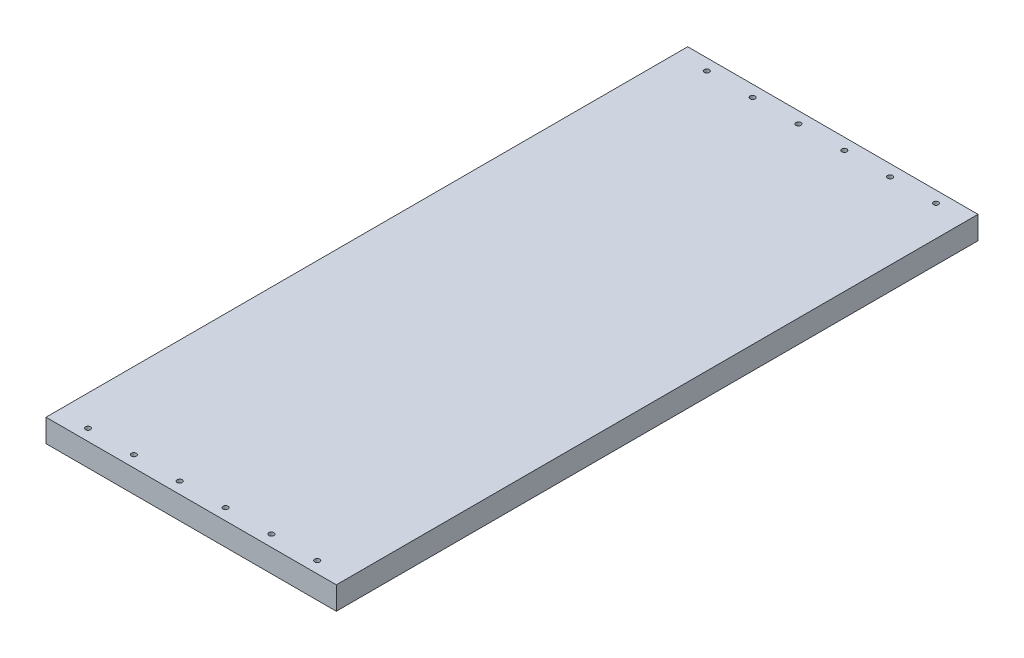
SolidWorks part; units mm, degrees
ref_plane "Front Plane" through (0, 0, 0) normal (0, 0, 1) x (1, 0, 0)
ref_plane "Top Plane" through (0, 0, 0) normal (0, 1, 0) x (1, 0, 0)
ref_plane "Right Plane" through (0, 0, 0) normal (1, 0, 0) x (0, 0, -1)
sketch "Sketch2" plane through (0, 0, 0) normal (0, 0, 1) x (1, 0, 0)
  line L1 (241.3, -19.05) -> (-241.3, -19.05)
  line L2 (241.3, -19.05) -> (241.3, 19.05)
  line L3 (241.3, 19.05) -> (-241.3, 19.05)
  line L4 (-241.3, -19.05) -> (-241.3, 19.05)
  line L5 (241.3, -19.05) -> (-241.3, 19.05) construction
  line L6 (241.3, 19.05) -> (-241.3, -19.05) construction
  point P0 (0, 0)
  dimension "D1" = 38.1
  dimension "D2" = 482.6
extrude "Boss-Extrude1" add sketch "Sketch2" along normal blind 1066.8
hole_wizard "CSK for 5/16 Flat Head Machine Screw1" positions "Sketch3" profile "Sketch4" countersink size "5/16" standard "ANSI Inch" end condition through all
sketch "Sketch3" plane through (0, -19.05, 0) normal (0, -1, 0) x (-1, 0, 0)
  line L0 (241.3, -1066.8) -> (-241.3, -1066.8) construction
  line L1 (241.3, -1066.8) -> (241.3, 0) construction
  line L2 (-241.3, -1066.8) -> (-241.3, 0) construction
  line L3 (241.3, 0) -> (-241.3, 0) construction
  point P0 (190.5, -1047.75)
  point P14 (114.3, -1047.75)
  point P15 (38.1, -1047.75)
  point P16 (-38.1, -1047.75)
  point P17 (-114.3, -1047.75)
  point P18 (-190.5, -1047.75)
  point P19 (114.3, -19.05)
  point P20 (38.1, -19.05)
  point P21 (-38.1, -19.05)
  point P22 (-114.3, -19.05)
  point P23 (-190.5, -19.05)
  point P24 (190.5, -19.05)
  dimension "D1" = 19.05
  dimension "D2" = 50.8
  dimension "D5" = 50.8
  dimension "D6" = 19.05
  dimension "D7" = 50.8
  dimension "D3" = 6
  dimension "D4" = 2
sketch "Sketch4" plane through (-190.5, -19.05, 1047.75) normal (1, 0, 0) x (0, 0, -1)
  line L0 (0, 0) -> (0, 38.1)
  line L1 (0, 38.1) -> (4.2164, 38.1)
  line L2 (4.2164, 38.1) -> (4.2164, 4.4267)
  line L3 (4.2164, 4.4267) -> (8.0645, 0)
  line L5 (8.0645, 0) -> (0, 0)
  line L6 (-4.2164, 4.4267) -> (-8.0645, 0) construction
  line L11 (0, -6.35) -> (0, 107.95) construction
  dimension "Thru Hole Dia." = 8.4328
  dimension "Thru Hole Depth" = 38.1
  dimension "Near C'Sink Dia." = 16.129
  dimension "Near C'Sink Angle" = 82
